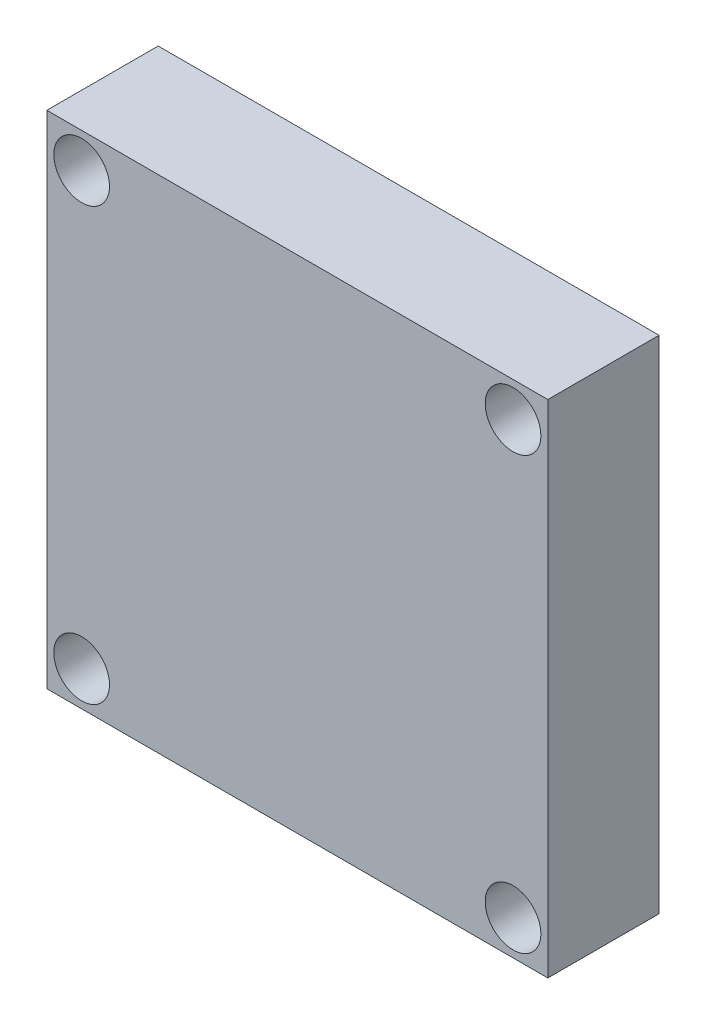
SolidWorks part; units mm, degrees
ref_plane "Front Plane" through (0, 0, 0) normal (0, 0, 1) x (1, 0, 0)
ref_plane "Top Plane" through (0, 0, 0) normal (0, 1, 0) x (1, 0, 0)
ref_plane "Right Plane" through (0, 0, 0) normal (1, 0, 0) x (0, 0, -1)
sketch "Sketch1" plane through (0, 0, 0) normal (0, 0, 1) x (1, 0, 0)
  line L1 (-18, -18) -> (18, -18)
  line L2 (-18, -18) -> (-18, 18)
  line L3 (-18, 18) -> (18, 18)
  line L4 (18, -18) -> (18, 18)
  line L5 (-18, -18) -> (18, 18) construction
  line L6 (-18, 18) -> (18, -18) construction
  line L7 (-15.5, -15.5) -> (15.5, -15.5) construction
  line L8 (-15.5, -15.5) -> (-15.5, 15.5) construction
  line L9 (-15.5, 15.5) -> (15.5, 15.5) construction
  line L10 (15.5, -15.5) -> (15.5, 15.5) construction
  line L11 (-15.5, -15.5) -> (15.5, 15.5) construction
  line L12 (-15.5, 15.5) -> (15.5, -15.5) construction
  circle A0 centre (-15.5, 15.5) radius 2
  circle A1 centre (15.5, 15.5) radius 2
  circle A2 centre (15.5, -15.5) radius 2
  circle A3 centre (-15.5, -15.5) radius 2
  point P0 (0, 0)
  point P6 (0, 0)
  point P15 (15.5, 0)
  dimension "D3" = 4
  dimension "D4" = 4
  dimension "D5" = 4
  dimension "D6" = 4
  dimension "D1" = 36
  dimension "D2" = 36
  dimension "D7" = 31
  dimension "D8" = 31
extrude "Boss-Extrude1" add sketch "Sketch1" along normal mid plane 8 contours A3 L1 A2 L4 A1 L3 A0 L2 region at (0, 0, 0)
